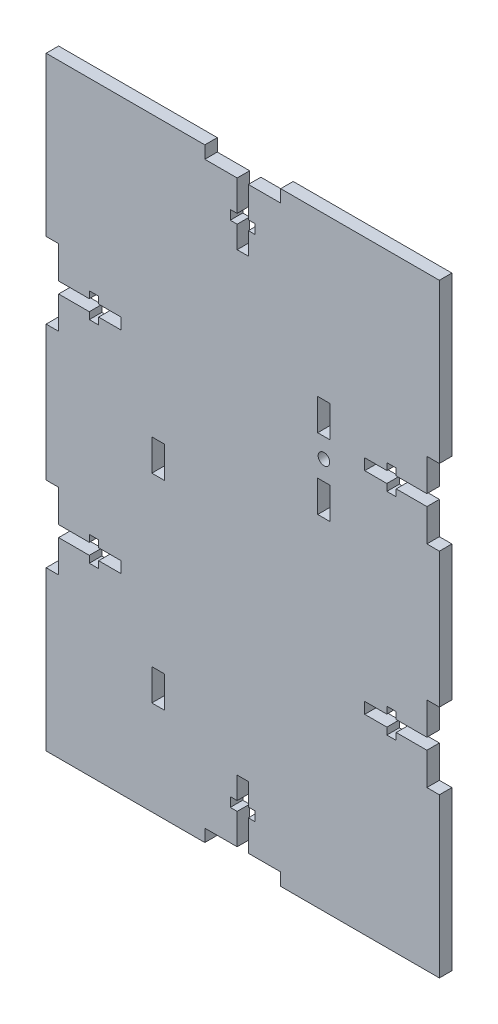
SolidWorks part; units mm, degrees
ref_plane "Front Plane" through (0, 0, 0) normal (0, 0, 1) x (1, 0, 0)
ref_plane "Top Plane" through (0, 0, 0) normal (0, 1, 0) x (1, 0, 0)
ref_plane "Right Plane" through (0, 0, 0) normal (1, 0, 0) x (0, 0, -1)
sketch "Sketch1" plane through (0, 0, 0) normal (0, 0, 1) x (1, 0, 0)
  line L0 (-50, 76.825) -> (-16.6667, 76.825)
  line L1 (-50, -76.825) -> (50, -76.825)
  line L2 (-50, -76.825) -> (-50, 76.825)
  line L3 (-50, 76.825) -> (50, 76.825) construction
  line L4 (50, -76.825) -> (50, 76.825)
  line L5 (-50, -76.825) -> (50, 76.825) construction
  line L6 (-50, 76.825) -> (50, -76.825) construction
  line L7 (-16.6667, 76.825) -> (16.6667, 76.825)
  line L8 (16.6667, 76.825) -> (50, 76.825)
  point P0 (0, 0)
  dimension "D1" = 100
  dimension "D2" = 153.65
extrude "Boss-Extrude1" add sketch "Sketch1" along normal blind 3.18
sketch "Sketch3" [suppressed] plane through (0, 0, 0) normal (0, 0, -1) x (-1, 0, 0)
  line L0 (-32.675, 34.075) -> (-32.675, -61.675)
  line L1 (-32.675, -61.675) -> (32.675, -61.675)
  line L2 (32.675, -61.675) -> (32.675, 34.075)
  line L3 (32.675, 34.075) -> (9.5, 34.075)
  line L4 (9.5, 34.075) -> (9.5, 37.075)
  line L5 (9.5, 37.075) -> (-9.5, 37.075)
  line L6 (-9.5, 37.075) -> (-9.5, 34.075)
  line L7 (-9.5, 34.075) -> (-32.675, 34.075)
  line L8 (32.675, 44.075) -> (-32.675, 44.075)
  line L9 (32.675, -61.675) -> (32.675, 44.075)
  line L10 (-32.675, -61.675) -> (32.675, -61.675)
  line L11 (-32.675, 44.075) -> (-32.675, -61.675)
  line L12 (-32.675, -61.675) -> (-32.675, -73.645) construction
  line L13 (44.645, -73.645) -> (-44.645, -73.645) construction
  line L14 (-32.675, -61.675) -> (-44.645, -61.675) construction
  line L15 (-44.645, -73.645) -> (-44.645, 73.645) construction
  line L16 (32.675, -61.675) -> (44.645, -61.675) construction
  line L17 (44.645, 73.645) -> (44.645, -73.645) construction
  dimension "D1" = 65.35
  dimension "D2" = 95.75
  dimension "D3" = 105.75
  dimension "D4" = 19
  dimension "D5" = 3
extrude "Cut-Extrude1" [suppressed] cut sketch "Sketch3" against normal through all contours L6 L7 L0 L1 L2 L3 L4 L5
sketch "Sketch9" [suppressed] plane through (-44.645, 0, 0) normal (-1, 0, 0) x (0, 0, 1)
  line L0 (0, 0) -> (3.18, 0) construction
  line L1 (0, 73.645) -> (0, -73.645) construction
  line L2 (3.18, 73.645) -> (3.18, -73.645) construction
  line L4 (0, -9.65) -> (3.18, -9.65)
  line L5 (0, -9.65) -> (0, 9.65)
  line L6 (0, 9.65) -> (3.18, 9.65)
  line L7 (3.18, -9.65) -> (3.18, 9.65)
  line L8 (0, -9.65) -> (3.18, 9.65) construction
  line L9 (0, 9.65) -> (3.18, -9.65) construction
  point P6 (1.59, 0)
  dimension "D1" = 19.3
extrude "Boss-Extrude4" [suppressed] add sketch "Sketch9" along normal blind 3.18
sketch "Sketch10" [suppressed] plane through (0, 0, 3.18) normal (0, 0, 1) x (1, 0, 0)
  line L0 (-46.235, 9.65) -> (-46.235, -9.65) construction
  line L1 (-47.825, 9.65) -> (-44.645, 9.65) construction
  line L2 (-47.825, -9.65) -> (-44.645, -9.65) construction
  circle A0 centre (-46.235, 0) radius 1.425
extrude "Cut-Extrude4" [suppressed] cut sketch "Sketch10" against normal through all
mirror "Mirror1" [suppressed] about plane through (0, 0, 0) normal (1, 0, 0)
sketch "Sketch18" [suppressed] plane through (44.645, 0, 0) normal (1, 0, 0) x (0, 0, -1)
  line L0 (0, 0) -> (-3.18, 0) construction
  line L1 (0, -73.645) -> (0, 73.645) construction
  line L2 (-3.18, -73.645) -> (-3.18, 73.645) construction
  line L4 (-3.18, -9.65) -> (0, -9.65)
  line L5 (-3.18, -9.65) -> (-3.18, 9.65)
  line L6 (-3.18, 9.65) -> (0, 9.65)
  line L7 (0, -9.65) -> (0, 9.65)
  line L8 (-3.18, -9.65) -> (0, 9.65) construction
  line L9 (-3.18, 9.65) -> (0, -9.65) construction
  point P6 (-1.59, 0)
  dimension "D1" = 19.3
extrude "Boss-Extrude8" [suppressed] add sketch "Sketch18" along normal blind 3.18
sketch "Sketch19" [suppressed] plane through (0, 0, 3.18) normal (0, 0, 1) x (1, 0, 0)
  line L0 (46.235, -9.65) -> (46.235, 9.65) construction
  line L1 (47.825, -9.65) -> (44.645, -9.65) construction
  line L2 (47.825, 9.65) -> (44.645, 9.65) construction
  circle A0 centre (46.235, 0) radius 1.425
extrude "Cut-Extrude8" [suppressed] cut sketch "Sketch19" against normal through all
mirror "Mirror2" [suppressed] about plane through (0, 0, 0) normal (1, 0, 0)
sketch "Sketch20" plane through (0, 0, 3.18) normal (0, 0, 1) x (1, 0, 0)
  line L0 (0, 70.465) -> (0, 0) construction
  line L1 (50, 76.825) -> (-50, 76.825) construction
  line L2 (-9.65, 76.825) -> (9.65, 76.825)
  line L3 (9.65, 76.825) -> (9.65, 73.645)
  line L4 (9.65, 73.645) -> (1.425, 73.645)
  line L5 (1.425, 73.645) -> (1.425, 65.845)
  line L6 (1.425, 65.845) -> (3.175, 65.845)
  line L7 (3.175, 65.845) -> (3.175, 63.465)
  line L8 (3.175, 63.465) -> (1.425, 63.465)
  line L9 (1.425, 63.465) -> (1.425, 57.845)
  line L10 (1.425, 57.845) -> (-1.425, 57.845)
  line L11 (-1.425, 57.845) -> (-1.425, 63.465)
  line L12 (-1.425, 63.465) -> (-3.175, 63.465)
  line L13 (-3.175, 63.465) -> (-3.175, 65.845)
  line L14 (-3.175, 65.845) -> (-1.425, 65.845)
  line L15 (-1.425, 65.845) -> (-1.425, 73.645)
  line L16 (-1.425, 73.645) -> (-9.65, 73.645)
  line L17 (-9.65, 73.645) -> (-9.65, 76.825)
  dimension "D1" = 19.3
  dimension "D2" = 3.18
  dimension "D3" = 15.8
  dimension "D4" = 6.35
  dimension "D5" = 2.38
  dimension "D6" = 2.85
  dimension "D7" = 7.8
extrude "Cut-Extrude9" cut sketch "Sketch20" against normal through all
mirror "Mirror3" about plane through (0, 0, 0) normal (0, 1, 0) of "Cut-Extrude9"
sketch "Sketch23" plane through (0, 0, 3.18) normal (0, 0, 1) x (1, 0, 0)
  line L0 (-50, 17.175) -> (-50, 36.475)
  line L1 (-50, 76.825) -> (-50, -76.825) construction
  line L2 (-50, 36.475) -> (-46.82, 36.475)
  line L3 (-46.82, 36.475) -> (-46.82, 28.25)
  line L4 (-46.82, 28.25) -> (-39.02, 28.25)
  line L5 (-39.02, 28.25) -> (-39.02, 30)
  line L6 (-39.02, 30) -> (-36.64, 30)
  line L7 (-36.64, 30) -> (-36.64, 28.25)
  line L8 (-36.64, 28.25) -> (-31.02, 28.25)
  line L9 (-31.02, 28.25) -> (-31.02, 25.4)
  line L10 (-31.02, 25.4) -> (-36.64, 25.4)
  line L11 (-36.64, 25.4) -> (-36.64, 23.65)
  line L12 (-36.64, 23.65) -> (-39.02, 23.65)
  line L13 (-39.02, 23.65) -> (-39.02, 25.4)
  line L14 (-39.02, 25.4) -> (-46.82, 25.4)
  line L15 (-46.82, 25.4) -> (-46.82, 17.175)
  line L16 (-46.82, 17.175) -> (-50, 17.175)
  line L17 (-9.65, 76.825) -> (-50, 76.825) construction
  line L19 (-31.02, 26.825) -> (-50, 26.825) construction
  line L20 (-50, -36.475) -> (-50, -17.175)
  line L21 (-50, -17.175) -> (-46.82, -17.175)
  line L22 (-46.82, -17.175) -> (-46.82, -25.4)
  line L23 (-46.82, -25.4) -> (-39.02, -25.4)
  line L24 (-39.02, -25.4) -> (-39.02, -23.65)
  line L25 (-39.02, -23.65) -> (-36.64, -23.65)
  line L26 (-36.64, -23.65) -> (-36.64, -25.4)
  line L27 (-36.64, -25.4) -> (-31.02, -25.4)
  line L28 (-31.02, -25.4) -> (-31.02, -28.25)
  line L29 (-31.02, -28.25) -> (-36.64, -28.25)
  line L30 (-36.64, -28.25) -> (-36.64, -30)
  line L31 (-36.64, -30) -> (-39.02, -30)
  line L32 (-39.02, -30) -> (-39.02, -28.25)
  line L33 (-39.02, -28.25) -> (-46.82, -28.25)
  line L34 (-46.82, -28.25) -> (-46.82, -36.475)
  line L35 (-46.82, -36.475) -> (-50, -36.475)
  line L36 (-50, -26.825) -> (-31.02, -26.825) construction
  line L37 (-50, -76.825) -> (-9.65, -76.825) construction
  dimension "D1" = 50
  dimension "D2" = 19.3
  dimension "D3" = 3.18
  dimension "D4" = 15.8
  dimension "D5" = 6.35
  dimension "D6" = 2.85
  dimension "D7" = 7.8
  dimension "D8" = 2.38
  dimension "D9" = 19.3
  dimension "D10" = 3.18
  dimension "D11" = 7.8
  dimension "D12" = 15.8
  dimension "D13" = 6.35
  dimension "D14" = 2.85
  dimension "D15" = 2.38
  dimension "D16" = 50
  dimension "D17" = 1.75
extrude "Cut-Extrude10" cut sketch "Sketch23" against normal through all
sketch "Sketch24" [suppressed] plane through (0, 0, 3.18) normal (0, 0, 1) x (1, 0, 0)
  line L0 (44.645, -13.995) -> (44.645, -33.295)
  line L1 (44.645, -73.645) -> (44.645, 73.645) construction
  line L2 (44.645, -33.295) -> (41.465, -33.295)
  line L3 (41.465, -33.295) -> (41.465, -25.07)
  line L4 (41.465, -25.07) -> (33.665, -25.07)
  line L5 (33.665, -25.07) -> (33.665, -26.82)
  line L6 (33.665, -26.82) -> (31.285, -26.82)
  line L7 (31.285, -26.82) -> (31.285, -25.07)
  line L8 (31.285, -25.07) -> (25.665, -25.07)
  line L9 (25.665, -25.07) -> (25.665, -22.22)
  line L10 (25.665, -22.22) -> (31.285, -22.22)
  line L11 (31.285, -22.22) -> (31.285, -20.47)
  line L12 (31.285, -20.47) -> (33.665, -20.47)
  line L13 (33.665, -20.47) -> (33.665, -22.22)
  line L14 (33.665, -22.22) -> (41.465, -22.22)
  line L15 (41.465, -22.22) -> (41.465, -13.995)
  line L16 (41.465, -13.995) -> (44.645, -13.995)
  line L17 (25.665, -23.645) -> (44.645, -23.645) construction
  line L18 (-44.645, -73.645) -> (44.645, -73.645) construction
  line L19 (44.645, 33.295) -> (44.645, 13.995)
  line L20 (44.645, 13.995) -> (41.465, 13.995)
  line L21 (41.465, 13.995) -> (41.465, 22.22)
  line L22 (41.465, 22.22) -> (33.665, 22.22)
  line L23 (33.665, 22.22) -> (33.665, 20.47)
  line L24 (33.665, 20.47) -> (31.285, 20.47)
  line L25 (31.285, 20.47) -> (31.285, 22.22)
  line L26 (31.285, 22.22) -> (25.665, 22.22)
  line L27 (25.665, 22.22) -> (25.665, 25.07)
  line L28 (25.665, 25.07) -> (31.285, 25.07)
  line L29 (31.285, 25.07) -> (31.285, 26.82)
  line L30 (31.285, 26.82) -> (33.665, 26.82)
  line L31 (33.665, 26.82) -> (33.665, 25.07)
  line L32 (33.665, 25.07) -> (41.465, 25.07)
  line L33 (41.465, 25.07) -> (41.465, 33.295)
  line L34 (41.465, 33.295) -> (44.645, 33.295)
  line L35 (25.665, 23.645) -> (44.645, 23.645) construction
  line L36 (44.645, 73.645) -> (-44.645, 73.645) construction
  dimension "D1" = 19.3
  dimension "D2" = 3.18
  dimension "D3" = 15.8
  dimension "D4" = 7.8
  dimension "D5" = 6.35
  dimension "D6" = 2.85
  dimension "D7" = 2.38
  dimension "D8" = 50
  dimension "D9" = 19.3
  dimension "D10" = 3.18
  dimension "D11" = 7.8
  dimension "D12" = 15.8
  dimension "D13" = 6.35
  dimension "D14" = 2.85
  dimension "D15" = 2.38
  dimension "D16" = 50
extrude "Cut-Extrude11" [suppressed] cut sketch "Sketch24" against normal through all
sketch "Sketch25" [suppressed] plane through (0, 0, 3.18) normal (0, 0, 1) x (1, 0, 0)
  line L0 (9.65, -73.645) -> (-9.65, -73.645)
  line L1 (-44.645, -73.645) -> (44.645, -73.645) construction
  line L2 (-9.65, -73.645) -> (-9.65, -70.465)
  line L3 (-9.65, -70.465) -> (-1.425, -70.465)
  line L4 (-1.425, -70.465) -> (-1.425, -62.665)
  line L5 (-1.425, -62.665) -> (-3.175, -62.665)
  line L6 (-3.175, -62.665) -> (-3.175, -60.285)
  line L7 (-3.175, -60.285) -> (-1.425, -60.285)
  line L8 (-1.425, -60.285) -> (-1.425, -54.665)
  line L9 (-1.425, -54.665) -> (1.425, -54.665)
  line L10 (1.425, -54.665) -> (1.425, -60.285)
  line L11 (1.425, -60.285) -> (3.175, -60.285)
  line L12 (3.175, -60.285) -> (3.175, -62.665)
  line L13 (3.175, -62.665) -> (1.425, -62.665)
  line L14 (1.425, -62.665) -> (1.425, -70.465)
  line L15 (1.425, -70.465) -> (9.65, -70.465)
  line L16 (9.65, -70.465) -> (9.65, -73.645)
  line L17 (0, -73.645) -> (0, 0) construction
  dimension "D1" = 19.3
  dimension "D2" = 3.18
  dimension "D3" = 15.8
  dimension "D4" = 7.8
  dimension "D5" = 6.35
  dimension "D6" = 2.85
  dimension "D7" = 2.38
extrude "Cut-Extrude12" [suppressed] cut sketch "Sketch25" against normal through all
sketch "Sketch26" [suppressed] plane through (0, 0, 3.18) normal (0, 0, 1) x (1, 0, 0)
  line L0 (-9.65, 73.645) -> (9.65, 73.645)
  line L1 (44.645, 73.645) -> (-44.645, 73.645) construction
  line L2 (9.65, 73.645) -> (9.65, 70.465)
  line L3 (9.65, 70.465) -> (1.425, 70.465)
  line L4 (1.425, 70.465) -> (1.425, 62.665)
  line L5 (1.425, 62.665) -> (3.175, 62.665)
  line L6 (3.175, 62.665) -> (3.175, 60.285)
  line L7 (3.175, 60.285) -> (1.425, 60.285)
  line L8 (1.425, 60.285) -> (1.425, 54.665)
  line L9 (1.425, 54.665) -> (-1.425, 54.665)
  line L10 (-1.425, 54.665) -> (-1.425, 60.285)
  line L11 (-1.425, 60.285) -> (-3.175, 60.285)
  line L12 (-3.175, 60.285) -> (-3.175, 62.665)
  line L13 (-3.175, 62.665) -> (-1.425, 62.665)
  line L14 (-1.425, 62.665) -> (-1.425, 70.465)
  line L15 (-1.425, 70.465) -> (-9.65, 70.465)
  line L16 (-9.65, 70.465) -> (-9.65, 73.645)
  line L17 (0, 73.645) -> (0, -4.4192) construction
  dimension "D1" = 19.3
  dimension "D2" = 3.18
  dimension "D3" = 7.8
  dimension "D4" = 15.8
  dimension "D5" = 6.35
  dimension "D6" = 2.85
  dimension "D7" = 2.38
extrude "Cut-Extrude13" [suppressed] cut sketch "Sketch26" against normal through all
mirror "Mirror4" about plane through (0, 0, 0) normal (1, 0, 0) of "Cut-Extrude10"
mirror "Mirror5" [suppressed] about plane through (0, 0, 0) normal (1, 0, 0)
mirror "Mirror6" [suppressed] about plane through (0, 0, 0) normal (0, 1, 0)
mirror "Mirror7" [suppressed] about plane through (0, 0, 0) normal (0, 1, 0)
sketch "Sketch27" [suppressed] plane through (-44.645, 0, 0) normal (-1, 0, 0) x (0, 0, 1)
  line L0 (0, -36.475) -> (0, -17.175)
  line L1 (0, 73.645) -> (0, -73.645) construction
  line L2 (0, -17.175) -> (3.18, -17.175)
  line L3 (3.18, 73.645) -> (3.18, -73.645) construction
  line L4 (3.18, -17.175) -> (3.18, -36.475)
  line L5 (3.18, -36.475) -> (0, -36.475)
  line L6 (3.18, -26.825) -> (0, -26.825) construction
  line L7 (3.18, -73.645) -> (0, -73.645) construction
  dimension "D1" = 19.3
  dimension "D2" = 46.82
extrude "Boss-Extrude9" [suppressed] add sketch "Sketch27" along normal blind 3.18
sketch "Sketch28" [suppressed] plane through (0, -73.645, 0) normal (0, -1, 0) x (1, 0, 0)
  line L0 (9.65, 0) -> (-9.65, 0)
  line L1 (-44.645, 0) -> (44.645, 0) construction
  line L2 (-9.65, 0) -> (-9.65, 3.18)
  line L3 (-44.645, 3.18) -> (44.645, 3.18) construction
  line L4 (-9.65, 3.18) -> (9.65, 3.18)
  line L5 (9.65, 3.18) -> (9.65, 0)
  line L6 (0, 0) -> (0, 3.18) construction
  dimension "D1" = 19.3
extrude "Boss-Extrude10" [suppressed] add sketch "Sketch28" along normal blind 3.18
sketch "Sketch29" [suppressed] plane through (0, 0, 3.18) normal (0, 0, 1) x (1, 0, 0)
  line L0 (-47.825, -26.825) -> (-37.3062, -26.825) construction
  line L1 (-47.825, -36.475) -> (-47.825, -17.175) construction
  line L2 (-46.235, -17.175) -> (-46.235, -36.475) construction
  line L3 (-47.825, -17.175) -> (-44.645, -17.175) construction
  line L4 (-47.825, -36.475) -> (-44.645, -36.475) construction
  circle A0 centre (-46.235, -26.825) radius 1.425
extrude "Cut-Extrude14" [suppressed] cut sketch "Sketch29" against normal through all
sketch "Sketch30" [suppressed] plane through (0, 0, 3.18) normal (0, 0, 1) x (1, 0, 0)
  line L0 (0, -76.825) -> (0, -66.2855) construction
  line L1 (9.65, -76.825) -> (-9.65, -76.825) construction
  line L2 (9.65, -75.235) -> (-9.65, -75.235) construction
  line L3 (9.65, -76.825) -> (9.65, -73.645) construction
  line L4 (-9.65, -76.825) -> (-9.65, -73.645) construction
  circle A0 centre (0, -75.235) radius 1.425
extrude "Cut-Extrude15" [suppressed] cut sketch "Sketch30" against normal through all
mirror "Mirror8" [suppressed] about plane through (0, 0, 0) normal (1, 0, 0)
mirror "Mirror9" [suppressed] about plane through (0, 0, 0) normal (0, 1, 0)
sketch "Sketch31" [suppressed] plane through (0, 0, 3.18) normal (0, 0, 1) x (1, 0, 0)
  line L0 (14.341, -8.1358) -> (14.341, -12.6358) construction
  line L8 (5.175, -1.9558) -> (5.175, 19.3642) construction
  line L10 (-24.825, 19.3642) -> (-24.825, -1.9558) construction
  line L11 (5.175, 19.3642) -> (-24.825, 19.3642) construction
  line L16 (23.507, -9.6358) -> (39.341, -9.6358) construction
  line L17 (23.507, 19.3642) -> (23.507, -9.6358) construction
  line L18 (39.341, 19.3642) -> (23.507, 19.3642) construction
  line L19 (39.341, -9.6358) -> (39.341, 19.3642) construction
  line L26 (14.341, -15.8158) -> (14.341, -12.6358) construction
  line L29 (-24.825, -1.9558) -> (5.175, -1.9558) construction
  line L34 (20.5772, -7.1358) -> (20.5772, 11.3642) construction
  line L35 (20.5772, 11.3642) -> (8.1048, 11.3642) construction
  line L36 (8.1048, 11.3642) -> (8.1048, -7.1358) construction
  line L37 (9.7431, -8.1358) -> (18.9389, -8.1358) construction
  line L38 (14.341, -15.8158) -> (14.341, -50) construction
  line L39 (-17.325, 9.65) -> (-24.825, 9.65) construction
  line L40 (-6.159, -12.4758) -> (34.841, -12.4758)
  line L41 (-6.159, -12.4758) -> (-6.159, -15.9758)
  line L42 (-6.159, -15.9758) -> (34.841, -15.9758)
  line L43 (34.841, -12.4758) -> (34.841, -15.9758)
  line L88 (-44.645, -50) -> (-9.65, -50) construction
  line L89 (-9.65, -50) -> (-9.65, -46.82) construction
  line L90 (-9.65, -46.82) -> (-1.425, -46.82) construction
  line L91 (-1.425, -46.82) -> (-1.425, -39.02) construction
  line L92 (-1.425, -39.02) -> (-3.175, -39.02) construction
  line L93 (-3.175, -39.02) -> (-3.175, -36.64) construction
  line L94 (-3.175, -36.64) -> (-1.425, -36.64) construction
  line L95 (-1.425, -36.64) -> (-1.425, -31.02) construction
  line L96 (-1.425, -31.02) -> (1.425, -31.02) construction
  line L97 (1.425, -31.02) -> (1.425, -36.64) construction
  line L98 (1.425, -36.64) -> (3.175, -36.64) construction
  line L99 (3.175, -36.64) -> (3.175, -39.02) construction
  line L100 (3.175, -39.02) -> (1.425, -39.02) construction
  line L101 (1.425, -39.02) -> (1.425, -46.82) construction
  line L102 (1.425, -46.82) -> (9.65, -46.82) construction
  line L103 (9.65, -46.82) -> (9.65, -50) construction
  line L104 (9.65, -50) -> (44.645, -50) construction
  line L105 (44.645, -50) -> (44.645, -9.65) construction
  line L106 (44.645, -9.65) -> (47.825, -9.65) construction
  line L107 (47.825, -9.65) -> (47.825, 9.65) construction
  line L108 (47.825, 9.65) -> (44.645, 9.65) construction
  line L109 (44.645, 9.65) -> (44.645, 50) construction
  line L110 (44.645, 50) -> (9.65, 50) construction
  line L111 (9.65, 50) -> (9.65, 46.82) construction
  line L112 (9.65, 46.82) -> (1.425, 46.82) construction
  line L113 (1.425, 46.82) -> (1.425, 39.02) construction
  line L114 (1.425, 39.02) -> (3.175, 39.02) construction
  line L115 (3.175, 39.02) -> (3.175, 36.64) construction
  line L116 (3.175, 36.64) -> (1.425, 36.64) construction
  line L117 (1.425, 36.64) -> (1.425, 31.02) construction
  line L118 (1.425, 31.02) -> (-1.425, 31.02) construction
  line L119 (-1.425, 31.02) -> (-1.425, 36.64) construction
  line L120 (-1.425, 36.64) -> (-3.175, 36.64) construction
  line L121 (-3.175, 36.64) -> (-3.175, 39.02) construction
  line L122 (-3.175, 39.02) -> (-1.425, 39.02) construction
  line L123 (-1.425, 39.02) -> (-1.425, 46.82) construction
  line L124 (-1.425, 46.82) -> (-9.65, 46.82) construction
  line L125 (-9.65, 46.82) -> (-9.65, 50) construction
  line L126 (-9.65, 50) -> (-44.645, 50) construction
  line L127 (-44.645, 50) -> (-44.645, 9.65) construction
  line L128 (-44.645, 9.65) -> (-47.825, 9.65) construction
  line L129 (-47.825, 9.65) -> (-47.825, -9.65) construction
  line L130 (-47.825, -9.65) -> (-44.645, -9.65) construction
  line L131 (-44.645, -9.65) -> (-44.645, -50) construction
  line L132 (-6.159, -12.4758) -> (34.841, -15.9758) construction
  line L133 (-6.159, -15.9758) -> (34.841, -12.4758) construction
  line L134 (-17.325, 9.65) -> (-17.325, -1.9558) construction
  line L135 (31.3061, 4.8642) -> (39.341, 4.8642) construction
  line L136 (31.3061, 4.8642) -> (31.3061, 19.3642) construction
  line L137 (-17.325, 9.65) -> (-4.325, 9.65) construction
  circle A0 centre (-17.325, 9.65) radius 1.5
  circle A1 centre (31.3061, 4.8642) radius 1.5
  circle A2 centre (-4.325, 9.65) radius 1.5
  spline S4 degree 3 poles (8.1048, -7.1358) (8.1048, -7.3148) (8.1799, -7.485) (8.4092, -7.7556) (8.5582, -7.8571) (8.8762, -8.0081) (9.0479, -8.0586) (9.3919, -8.1221) (9.5665, -8.1358) (9.7431, -8.1358) knots 0 0 0 0 0.25 0.25 0.5 0.5 0.75 0.75 1 1 1 1 construction
  spline S5 degree 3 poles (18.9389, -8.1358) (19.1156, -8.1358) (19.2906, -8.1221) (19.6363, -8.0581) (19.8071, -8.0076) (20.1239, -7.857) (20.2729, -7.7556) (20.5025, -7.4843) (20.5772, -7.3148) (20.5772, -7.1358) knots 0 0 0 0 0.25 0.25 0.5 0.5 0.75 0.75 1 1 1 1 construction
  point P14 (14.341, -14.2258)
  point P46 (-44.645, 73.645)
  dimension "D6" = 3
  dimension "D4" = 41
  dimension "D5" = 3.5
  dimension "D7" = 7.5
  dimension "D9" = 13
extrude "Cut-Extrude16" [suppressed] cut sketch "Sketch31" against normal through all contours L41 L40 L43 L42 | A1 | A2 | A0
sketch "Sketch32" plane through (0, 0, 3.18) normal (0, 0, 1) x (1, 0, 0)
  line L0 (22.24, 17.7829) -> (22.24, 9.7829)
  line L1 (22.24, 35.7829) -> (22.24, 27.7829)
  line L2 (22.24, 35.7829) -> (19.06, 35.7829)
  line L3 (22.24, 35.7829) -> (22.24, 27.7829)
  line L4 (22.24, 27.7829) -> (19.06, 27.7829)
  line L5 (19.06, 35.7829) -> (19.06, 27.7829)
  line L6 (22.24, 17.7829) -> (19.06, 17.7829)
  line L7 (22.24, 17.7829) -> (22.24, 9.7829)
  line L8 (22.24, 9.7829) -> (19.06, 9.7829)
  line L9 (19.06, 17.7829) -> (19.06, 9.7829)
  line L10 (22.24, 17.7829) -> (22.24, 27.7829) construction
  line L11 (50, -17.175) -> (50, 17.175) construction
  line L12 (50, 17.175) -> (46.82, 17.175) construction
  line L13 (46.82, 17.175) -> (46.82, 25.4) construction
  line L14 (46.82, 25.4) -> (39.02, 25.4) construction
  line L15 (39.02, 25.4) -> (39.02, 23.65) construction
  line L16 (39.02, 23.65) -> (36.64, 23.65) construction
  line L17 (36.64, 23.65) -> (36.64, 25.4) construction
  line L18 (36.64, 25.4) -> (31.02, 25.4) construction
  line L19 (31.02, 25.4) -> (31.02, 28.25) construction
  line L20 (31.02, 28.25) -> (36.64, 28.25) construction
  line L21 (36.64, 28.25) -> (36.64, 30) construction
  line L22 (36.64, 30) -> (39.02, 30) construction
  line L23 (39.02, 30) -> (39.02, 28.25) construction
  line L24 (39.02, 28.25) -> (46.82, 28.25) construction
  line L25 (46.82, 28.25) -> (46.82, 36.475) construction
  line L26 (46.82, 36.475) -> (50, 36.475) construction
  line L27 (50, 36.475) -> (50, 76.825) construction
  line L28 (50, 76.825) -> (9.65, 76.825) construction
  line L29 (9.65, 76.825) -> (9.65, 73.645) construction
  line L30 (9.65, 73.645) -> (1.425, 73.645) construction
  line L31 (1.425, 73.645) -> (1.425, 65.845) construction
  line L32 (1.425, 65.845) -> (3.175, 65.845) construction
  line L33 (3.175, 65.845) -> (3.175, 63.465) construction
  line L34 (3.175, 63.465) -> (1.425, 63.465) construction
  line L35 (1.425, 63.465) -> (1.425, 57.845) construction
  line L36 (1.425, 57.845) -> (-1.425, 57.845) construction
  line L37 (-1.425, 57.845) -> (-1.425, 63.465) construction
  line L38 (-1.425, 63.465) -> (-3.175, 63.465) construction
  line L39 (-3.175, 63.465) -> (-3.175, 65.845) construction
  line L40 (-3.175, 65.845) -> (-1.425, 65.845) construction
  line L41 (-1.425, 65.845) -> (-1.425, 73.645) construction
  line L42 (-1.425, 73.645) -> (-9.65, 73.645) construction
  line L43 (-9.65, 73.645) -> (-9.65, 76.825) construction
  line L44 (-9.65, 76.825) -> (-50, 76.825) construction
  line L45 (-50, 76.825) -> (-50, 36.475) construction
  line L46 (-50, 36.475) -> (-46.82, 36.475) construction
  line L47 (-46.82, 36.475) -> (-46.82, 28.25) construction
  line L48 (-46.82, 28.25) -> (-39.02, 28.25) construction
  line L49 (-39.02, 28.25) -> (-39.02, 30) construction
  line L50 (-39.02, 30) -> (-36.64, 30) construction
  line L51 (-36.64, 30) -> (-36.64, 28.25) construction
  line L52 (-36.64, 28.25) -> (-31.02, 28.25) construction
  line L53 (-31.02, 28.25) -> (-31.02, 25.4) construction
  line L54 (-31.02, 25.4) -> (-36.64, 25.4) construction
  line L55 (-36.64, 25.4) -> (-36.64, 23.65) construction
  line L56 (-36.64, 23.65) -> (-39.02, 23.65) construction
  line L57 (-39.02, 23.65) -> (-39.02, 25.4) construction
  line L58 (-39.02, 25.4) -> (-46.82, 25.4) construction
  line L59 (-46.82, 25.4) -> (-46.82, 17.175) construction
  line L60 (-46.82, 17.175) -> (-50, 17.175) construction
  line L61 (-50, 17.175) -> (-50, -17.175) construction
  line L62 (-50, -17.175) -> (-46.82, -17.175) construction
  line L63 (-46.82, -17.175) -> (-46.82, -25.4) construction
  line L64 (-46.82, -25.4) -> (-39.02, -25.4) construction
  line L65 (-39.02, -25.4) -> (-39.02, -23.65) construction
  line L66 (-39.02, -23.65) -> (-36.64, -23.65) construction
  line L67 (-36.64, -23.65) -> (-36.64, -25.4) construction
  line L68 (-36.64, -25.4) -> (-31.02, -25.4) construction
  line L69 (-31.02, -25.4) -> (-31.02, -28.25) construction
  line L70 (-31.02, -28.25) -> (-36.64, -28.25) construction
  line L71 (-36.64, -28.25) -> (-36.64, -30) construction
  line L72 (-36.64, -30) -> (-39.02, -30) construction
  line L73 (-39.02, -30) -> (-39.02, -28.25) construction
  line L74 (-39.02, -28.25) -> (-46.82, -28.25) construction
  line L75 (-46.82, -28.25) -> (-46.82, -36.475) construction
  line L76 (-46.82, -36.475) -> (-50, -36.475) construction
  line L77 (-50, -36.475) -> (-50, -76.825) construction
  line L78 (-50, -76.825) -> (-9.65, -76.825) construction
  line L79 (-9.65, -76.825) -> (-9.65, -73.645) construction
  line L80 (-9.65, -73.645) -> (-1.425, -73.645) construction
  line L81 (-1.425, -73.645) -> (-1.425, -65.845) construction
  line L82 (-1.425, -65.845) -> (-3.175, -65.845) construction
  line L83 (-3.175, -65.845) -> (-3.175, -63.465) construction
  line L84 (-3.175, -63.465) -> (-1.425, -63.465) construction
  line L85 (-1.425, -63.465) -> (-1.425, -57.845) construction
  line L86 (-1.425, -57.845) -> (1.425, -57.845) construction
  line L87 (1.425, -57.845) -> (1.425, -63.465) construction
  line L88 (1.425, -63.465) -> (3.175, -63.465) construction
  line L89 (3.175, -63.465) -> (3.175, -65.845) construction
  line L90 (3.175, -65.845) -> (1.425, -65.845) construction
  line L91 (1.425, -65.845) -> (1.425, -73.645) construction
  line L92 (1.425, -73.645) -> (9.65, -73.645) construction
  line L93 (9.65, -73.645) -> (9.65, -76.825) construction
  line L94 (9.65, -76.825) -> (50, -76.825) construction
  line L95 (50, -76.825) -> (50, -36.475) construction
  line L96 (50, -36.475) -> (46.82, -36.475) construction
  line L97 (46.82, -36.475) -> (46.82, -28.25) construction
  line L98 (46.82, -28.25) -> (39.02, -28.25) construction
  line L99 (39.02, -28.25) -> (39.02, -30) construction
  line L100 (39.02, -30) -> (36.64, -30) construction
  line L101 (36.64, -30) -> (36.64, -28.25) construction
  line L102 (36.64, -28.25) -> (31.02, -28.25) construction
  line L103 (31.02, -28.25) -> (31.02, -25.4) construction
  line L104 (31.02, -25.4) -> (36.64, -25.4) construction
  line L105 (36.64, -25.4) -> (36.64, -23.65) construction
  line L106 (36.64, -23.65) -> (39.02, -23.65) construction
  line L107 (39.02, -23.65) -> (39.02, -25.4) construction
  line L108 (39.02, -25.4) -> (46.82, -25.4) construction
  line L109 (46.82, -25.4) -> (46.82, -17.175) construction
  line L110 (46.82, -17.175) -> (50, -17.175) construction
  line L111 (20.65, 27.7829) -> (20.65, 17.7829) construction
  line L112 (0, 0) -> (0, 57.845) construction
  line L113 (-20.65, 27.7829) -> (-20.65, 17.7829) construction
  line L114 (-22.24, 17.7829) -> (-22.24, 27.7829) construction
  line L115 (-19.06, 17.7829) -> (-19.06, 9.7829)
  line L116 (-22.24, 9.7829) -> (-19.06, 9.7829)
  line L117 (-22.24, 17.7829) -> (-22.24, 9.7829)
  line L118 (-22.24, 17.7829) -> (-19.06, 17.7829)
  line L119 (-19.06, 35.7829) -> (-19.06, 27.7829)
  line L120 (-22.24, 27.7829) -> (-19.06, 27.7829)
  line L121 (-22.24, 35.7829) -> (-22.24, 27.7829)
  line L122 (-22.24, 35.7829) -> (-19.06, 35.7829)
  line L123 (-22.24, 35.7829) -> (-22.24, 27.7829)
  line L124 (-22.24, 17.7829) -> (-22.24, 9.7829)
  circle A0 centre (20.65, 22.7829) radius 1.47
  circle A1 centre (-20.65, 22.7829) radius 1.47
  dimension "D1" = 2.94
extrude "Cut-Extrude17" [suppressed] cut sketch "Sketch32" against normal through all contours L118 L117 L116 L115 | L122 L121 L120 L119 | A1
extrude "Cut-Extrude18" cut sketch "Sketch32<4>" against normal through all contours L2 L5 L4 L1 | A0 | L6 L9 L8 L0 region at (20.65, 13.7829, 3.18) region at (20.65, 31.7829, 3.18) region at (20.65, 22.7829, 3.18)
sketch "Sketch32<4>" plane through (0, 0, 3.18) normal (0, 0, 1) x (1, 0, 0) same geometry as "Sketch32"
sketch "Sketch33" plane through (0, 0, 0) normal (0, 0, 1) x (1, 0, 0)
  line L108 (-23.12, -44.8116) -> (-23.12, -52.8116)
  line L109 (-23.12, -52.8116) -> (-19.94, -52.8116)
  line L110 (-19.94, -52.8116) -> (-19.94, -44.8116)
  line L111 (-19.94, -44.8116) -> (-23.12, -44.8116)
  line L112 (-23.12, 5.7884) -> (-23.12, -2.2116)
  line L113 (-23.12, -2.2116) -> (-19.94, -2.2116)
  line L114 (-19.94, -2.2116) -> (-19.94, 5.7884)
  line L115 (-19.94, 5.7884) -> (-23.12, 5.7884)
extrude "Cut-Extrude22" cut sketch "Sketch33" along normal through all
